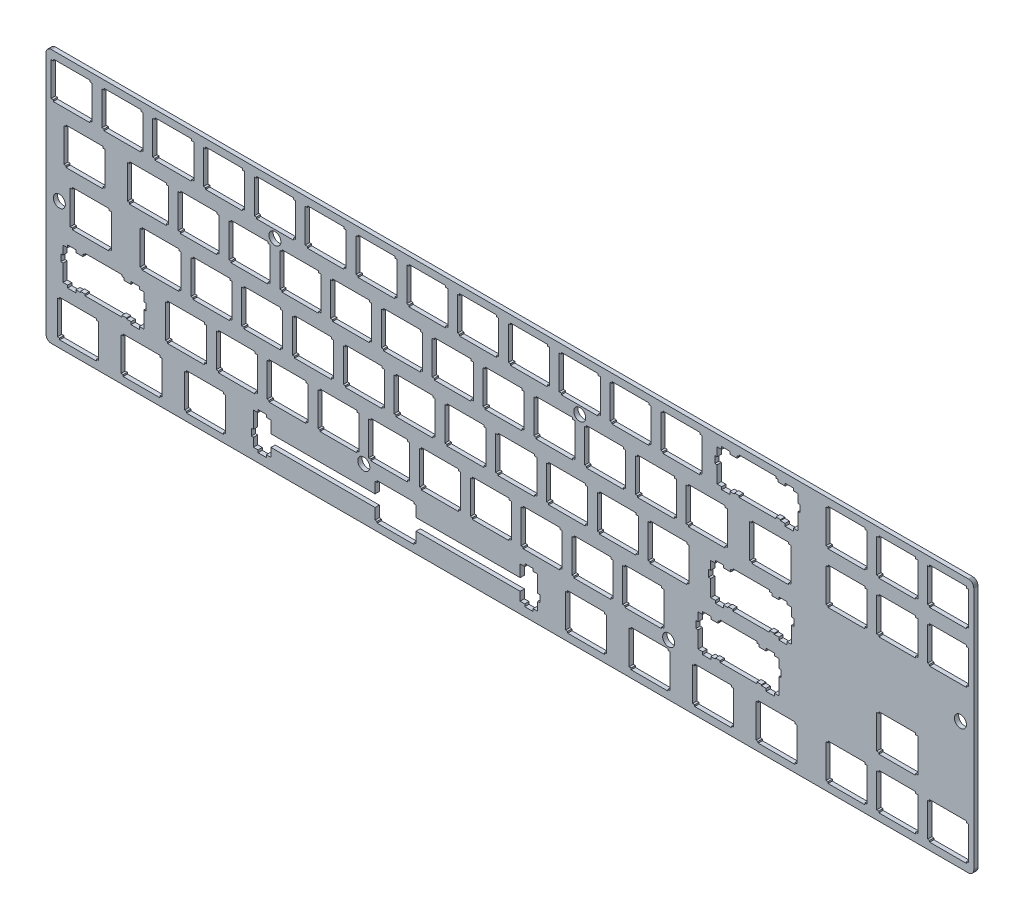
SolidWorks part; units mm, degrees
material "Brass"
ref_plane "Front Plane" through (0, 0, 0) normal (0, 0, 1) x (1, 0, 0)
ref_plane "Top Plane" through (0, 0, 0) normal (0, 1, 0) x (1, 0, 0)
ref_plane "Right Plane" through (0, 0, 0) normal (1, 0, 0) x (0, 0, -1)
sketch "Model" plane through (0, 0, 0) normal (0, 0, 1) x (1, 0, 0)
  line L0 (162.6206, 107.1381) -> (162.6206, 107.7376)
  line L1 (162.6206, 107.7376) -> (163.4196, 107.7376)
  line L2 (163.4196, 107.7376) -> (163.4196, 111.8386)
  line L3 (163.4196, 111.8386) -> (202.4455, 111.8386)
  line L4 (202.4455, 111.8386) -> (202.4455, 108.6085)
  line L5 (202.4455, 108.6085) -> (204.1696, 108.6085)
  line L6 (204.1696, 108.6085) -> (204.1696, 107.6893)
  line L7 (204.1696, 107.6893) -> (207.2701, 107.6893)
  line L8 (207.2701, 107.6893) -> (207.2701, 108.6085)
  line L9 (207.2701, 108.6085) -> (208.9956, 108.6085)
  line L10 (208.9956, 108.6085) -> (208.9956, 111.8386)
  line L11 (208.9956, 111.8386) -> (209.8196, 111.8386)
  line L12 (209.8196, 111.8386) -> (209.8196, 114.4389)
  line L13 (209.8196, 114.4389) -> (208.9956, 114.4389)
  line L14 (208.9956, 114.4389) -> (208.9956, 120.7076)
  line L15 (208.9956, 120.7076) -> (207.2701, 120.7076)
  line L16 (207.2701, 120.7076) -> (207.2701, 121.6888)
  line L17 (207.2701, 121.6888) -> (204.1696, 121.6888)
  line L18 (204.1696, 121.6888) -> (204.1696, 120.7076)
  line L19 (204.1696, 120.7076) -> (202.4455, 120.7076)
  line L20 (202.4455, 120.7076) -> (202.4455, 116.2387)
  line L21 (202.4455, 116.2387) -> (163.4196, 116.2387)
  line L22 (163.4196, 116.2387) -> (163.4196, 120.3383)
  line L23 (163.4196, 120.3383) -> (162.6206, 120.3383)
  line L24 (162.6206, 120.3383) -> (162.6206, 120.9391)
  line L25 (162.6206, 120.9391) -> (148.8206, 120.9391)
  line L26 (148.8206, 120.9391) -> (148.8206, 120.3383)
  line L27 (148.8206, 120.3383) -> (148.0196, 120.3383)
  line L28 (148.0196, 120.3383) -> (148.0196, 116.2387)
  line L29 (148.0196, 116.2387) -> (108.9956, 116.2387)
  line L30 (108.9956, 116.2387) -> (108.9956, 120.7076)
  line L31 (108.9956, 120.7076) -> (107.2696, 120.7076)
  line L32 (107.2696, 120.7076) -> (107.2696, 121.6888)
  line L33 (107.2696, 121.6888) -> (104.1696, 121.6888)
  line L34 (104.1696, 121.6888) -> (104.1696, 120.7076)
  line L35 (104.1696, 120.7076) -> (102.4456, 120.7076)
  line L36 (102.4456, 120.7076) -> (102.4456, 114.4389)
  line L37 (102.4456, 114.4389) -> (101.6206, 114.4389)
  line L38 (101.6206, 114.4389) -> (101.6206, 111.8386)
  line L39 (101.6206, 111.8386) -> (102.4456, 111.8386)
  line L40 (102.4456, 111.8386) -> (102.4456, 108.6085)
  line L41 (102.4456, 108.6085) -> (104.1696, 108.6085)
  line L42 (104.1696, 108.6085) -> (104.1696, 107.6893)
  line L43 (104.1696, 107.6893) -> (107.2696, 107.6893)
  line L44 (107.2696, 107.6893) -> (107.2696, 108.6085)
  line L45 (107.2696, 108.6085) -> (108.9956, 108.6085)
  line L46 (108.9956, 108.6085) -> (108.9956, 111.8386)
  line L47 (108.9956, 111.8386) -> (148.0196, 111.8386)
  line L48 (148.0196, 111.8386) -> (148.0196, 107.7376)
  line L49 (148.0196, 107.7376) -> (148.8206, 107.7376)
  line L50 (148.8206, 107.7376) -> (148.8206, 107.1381)
  line L51 (148.8206, 107.1381) -> (162.6206, 107.1381)
  line L52 (355.9896, 120.9391) -> (355.9896, 120.3396)
  line L53 (355.9896, 120.3396) -> (355.1906, 120.3396)
  line L54 (355.1906, 120.3396) -> (355.1906, 107.7389)
  line L55 (355.1906, 107.7389) -> (355.9896, 107.7389)
  line L56 (355.9896, 107.7389) -> (355.9896, 107.1381)
  line L57 (355.9896, 107.1381) -> (369.7906, 107.1381)
  line L58 (369.7906, 107.1381) -> (369.7906, 107.7389)
  line L59 (369.7906, 107.7389) -> (370.5896, 107.7389)
  line L60 (370.5896, 107.7389) -> (370.5896, 120.3396)
  line L61 (370.5896, 120.3396) -> (369.7906, 120.3396)
  line L62 (369.7906, 120.3396) -> (369.7906, 120.9391)
  line L63 (369.7906, 120.9391) -> (355.9896, 120.9391)
  line L64 (336.9396, 120.9391) -> (336.9396, 120.3396)
  line L65 (336.9396, 120.3396) -> (336.1406, 120.3396)
  line L66 (336.1406, 120.3396) -> (336.1406, 107.7389)
  line L67 (336.1406, 107.7389) -> (336.9396, 107.7389)
  line L68 (336.9396, 107.7389) -> (336.9396, 107.1381)
  line L69 (336.9396, 107.1381) -> (350.7406, 107.1381)
  line L70 (350.7406, 107.1381) -> (350.7406, 107.7389)
  line L71 (350.7406, 107.7389) -> (351.5396, 107.7389)
  line L72 (351.5396, 107.7389) -> (351.5396, 120.3396)
  line L73 (351.5396, 120.3396) -> (350.7406, 120.3396)
  line L74 (350.7406, 120.3396) -> (350.7406, 120.9391)
  line L75 (350.7406, 120.9391) -> (336.9396, 120.9391)
  line L76 (317.8896, 120.9391) -> (317.8896, 120.3396)
  line L77 (317.8896, 120.3396) -> (317.0906, 120.3396)
  line L78 (317.0906, 120.3396) -> (317.0906, 107.7389)
  line L79 (317.0906, 107.7389) -> (317.8896, 107.7389)
  line L80 (317.8896, 107.7389) -> (317.8896, 107.1381)
  line L81 (317.8896, 107.1381) -> (331.6906, 107.1381)
  line L82 (331.6906, 107.1381) -> (331.6906, 107.7389)
  line L83 (331.6906, 107.7389) -> (332.4896, 107.7389)
  line L84 (332.4896, 107.7389) -> (332.4896, 120.3396)
  line L85 (332.4896, 120.3396) -> (331.6906, 120.3396)
  line L86 (331.6906, 120.3396) -> (331.6906, 120.9391)
  line L87 (331.6906, 120.9391) -> (317.8896, 120.9391)
  line L88 (291.6956, 120.9391) -> (291.6956, 120.3396)
  line L89 (291.6956, 120.3396) -> (290.8966, 120.3396)
  line L90 (290.8966, 120.3396) -> (290.8966, 107.7389)
  line L91 (290.8966, 107.7389) -> (291.6956, 107.7389)
  line L92 (291.6956, 107.7389) -> (291.6956, 107.1381)
  line L93 (291.6956, 107.1381) -> (305.4956, 107.1381)
  line L94 (305.4956, 107.1381) -> (305.4956, 107.7389)
  line L95 (305.4956, 107.7389) -> (306.2966, 107.7389)
  line L96 (306.2966, 107.7389) -> (306.2966, 120.3396)
  line L97 (306.2966, 120.3396) -> (305.4956, 120.3396)
  line L98 (305.4956, 120.3396) -> (305.4956, 120.9391)
  line L99 (305.4956, 120.9391) -> (291.6956, 120.9391)
  line L100 (267.8846, 120.9391) -> (267.8846, 120.3396)
  line L101 (267.8846, 120.3396) -> (267.0846, 120.3396)
  line L102 (267.0846, 120.3396) -> (267.0846, 107.7389)
  line L103 (267.0846, 107.7389) -> (267.8846, 107.7389)
  line L104 (267.8846, 107.7389) -> (267.8846, 107.1381)
  line L105 (267.8846, 107.1381) -> (281.6846, 107.1381)
  line L106 (281.6846, 107.1381) -> (281.6846, 107.7389)
  line L107 (281.6846, 107.7389) -> (282.4836, 107.7389)
  line L108 (282.4836, 107.7389) -> (282.4836, 120.3396)
  line L109 (282.4836, 120.3396) -> (281.6846, 120.3396)
  line L110 (281.6846, 120.3396) -> (281.6846, 120.9391)
  line L111 (281.6846, 120.9391) -> (267.8846, 120.9391)
  line L112 (244.0706, 120.9391) -> (244.0706, 120.3396)
  line L113 (244.0706, 120.3396) -> (243.2716, 120.3396)
  line L114 (243.2716, 120.3396) -> (243.2716, 107.7389)
  line L115 (243.2716, 107.7389) -> (244.0706, 107.7389)
  line L116 (244.0706, 107.7389) -> (244.0706, 107.1381)
  line L117 (244.0706, 107.1381) -> (257.8706, 107.1381)
  line L118 (257.8706, 107.1381) -> (257.8706, 107.7389)
  line L119 (257.8706, 107.7389) -> (258.6716, 107.7389)
  line L120 (258.6716, 107.7389) -> (258.6716, 120.3396)
  line L121 (258.6716, 120.3396) -> (257.8706, 120.3396)
  line L122 (257.8706, 120.3396) -> (257.8706, 120.9391)
  line L123 (257.8706, 120.9391) -> (244.0706, 120.9391)
  line L124 (220.2596, 120.9391) -> (220.2596, 120.3396)
  line L125 (220.2596, 120.3396) -> (219.4596, 120.3396)
  line L126 (219.4596, 120.3396) -> (219.4596, 107.7389)
  line L127 (219.4596, 107.7389) -> (220.2596, 107.7389)
  line L128 (220.2596, 107.7389) -> (220.2596, 107.1381)
  line L129 (220.2596, 107.1381) -> (234.0596, 107.1381)
  line L130 (234.0596, 107.1381) -> (234.0596, 107.7389)
  line L131 (234.0596, 107.7389) -> (234.8586, 107.7389)
  line L132 (234.8586, 107.7389) -> (234.8586, 120.3396)
  line L133 (234.8586, 120.3396) -> (234.0596, 120.3396)
  line L134 (234.0596, 120.3396) -> (234.0596, 120.9391)
  line L135 (234.0596, 120.9391) -> (220.2596, 120.9391)
  line L136 (77.3847, 120.9391) -> (77.3847, 120.3396)
  line L137 (77.3847, 120.3396) -> (76.5842, 120.3396)
  line L138 (76.5842, 120.3396) -> (76.5842, 107.7389)
  line L139 (76.5842, 107.7389) -> (77.3847, 107.7389)
  line L140 (77.3847, 107.7389) -> (77.3847, 107.1381)
  line L141 (77.3847, 107.1381) -> (91.1843, 107.1381)
  line L142 (91.1843, 107.1381) -> (91.1843, 107.7389)
  line L143 (91.1843, 107.7389) -> (91.9837, 107.7389)
  line L144 (91.9837, 107.7389) -> (91.9837, 120.3396)
  line L145 (91.9837, 120.3396) -> (91.1843, 120.3396)
  line L146 (91.1843, 120.3396) -> (91.1843, 120.9391)
  line L147 (91.1843, 120.9391) -> (77.3847, 120.9391)
  line L148 (53.5708, 120.9391) -> (53.5708, 120.3396)
  line L149 (53.5708, 120.3396) -> (52.7716, 120.3396)
  line L150 (52.7716, 120.3396) -> (52.7716, 107.7389)
  line L151 (52.7716, 107.7389) -> (53.5708, 107.7389)
  line L152 (53.5708, 107.7389) -> (53.5708, 107.1381)
  line L153 (53.5708, 107.1381) -> (67.3704, 107.1381)
  line L154 (67.3704, 107.1381) -> (67.3704, 107.7389)
  line L155 (67.3704, 107.7389) -> (68.1712, 107.7389)
  line L156 (68.1712, 107.7389) -> (68.1712, 120.3396)
  line L157 (68.1712, 120.3396) -> (67.3704, 120.3396)
  line L158 (67.3704, 120.3396) -> (67.3704, 120.9391)
  line L159 (67.3704, 120.9391) -> (53.5708, 120.9391)
  line L160 (29.7597, 120.9391) -> (29.7597, 120.3396)
  line L161 (29.7597, 120.3396) -> (28.959, 120.3396)
  line L162 (28.959, 120.3396) -> (28.959, 107.7389)
  line L163 (28.959, 107.7389) -> (29.7597, 107.7389)
  line L164 (29.7597, 107.7389) -> (29.7597, 107.1381)
  line L165 (29.7597, 107.1381) -> (43.5594, 107.1381)
  line L166 (43.5594, 107.1381) -> (43.5594, 107.7389)
  line L167 (43.5594, 107.7389) -> (44.3586, 107.7389)
  line L168 (44.3586, 107.7389) -> (44.3586, 120.3396)
  line L169 (44.3586, 120.3396) -> (43.5594, 120.3396)
  line L170 (43.5594, 120.3396) -> (43.5594, 120.9391)
  line L171 (43.5594, 120.9391) -> (29.7597, 120.9391)
  line L172 (277.4086, 139.9906) -> (277.4086, 139.3898)
  line L173 (277.4086, 139.3898) -> (276.6096, 139.3898)
  line L174 (276.6096, 139.3898) -> (276.6096, 138.5187)
  line L175 (275.6846, 138.5187) -> (273.9596, 138.5187)
  line L176 (273.9596, 138.5187) -> (273.9596, 139.4378)
  line L177 (273.9596, 139.4378) -> (270.8586, 139.4378)
  line L178 (270.8586, 139.4378) -> (270.8586, 138.5187)
  line L179 (270.8586, 138.5187) -> (269.1346, 138.5187)
  line L180 (269.1346, 138.5187) -> (269.1346, 135.2886)
  line L181 (269.1346, 135.2886) -> (268.3086, 135.2886)
  line L182 (268.3086, 135.2886) -> (268.3086, 132.6882)
  line L183 (268.3086, 132.6882) -> (269.1346, 132.6882)
  line L184 (269.1346, 132.6882) -> (269.1346, 126.4182)
  line L185 (269.1346, 126.4182) -> (270.8586, 126.4182)
  line L186 (270.8586, 126.4182) -> (270.8586, 125.4384)
  line L187 (270.8586, 125.4384) -> (273.9596, 125.4384)
  line L188 (273.9596, 125.4384) -> (273.9596, 126.4182)
  line L189 (273.9596, 126.4182) -> (275.6846, 126.4182)
  line L190 (275.6846, 126.4182) -> (275.6846, 126.7888)
  line L191 (276.6096, 126.7888) -> (277.4086, 126.7888)
  line L192 (277.4086, 126.7888) -> (277.4086, 126.188)
  line L193 (277.4086, 126.188) -> (291.2096, 126.188)
  line L194 (291.2096, 126.188) -> (291.2096, 126.7888)
  line L195 (291.2096, 126.7888) -> (292.0086, 126.7888)
  line L196 (292.9346, 126.7888) -> (292.9346, 126.4182)
  line L197 (292.9346, 126.4182) -> (294.6586, 126.4182)
  line L198 (294.6586, 126.4182) -> (294.6586, 125.4384)
  line L199 (294.6586, 125.4384) -> (297.7596, 125.4384)
  line L200 (297.7596, 125.4384) -> (297.7596, 126.4182)
  line L201 (297.7596, 126.4182) -> (299.4846, 126.4182)
  line L202 (299.4846, 126.4182) -> (299.4846, 132.6882)
  line L203 (299.4846, 132.6882) -> (300.3086, 132.6882)
  line L204 (300.3086, 132.6882) -> (300.3086, 135.2886)
  line L205 (300.3086, 135.2886) -> (299.4846, 135.2886)
  line L206 (299.4846, 135.2886) -> (299.4846, 138.5187)
  line L207 (299.4846, 138.5187) -> (297.7596, 138.5187)
  line L208 (297.7596, 138.5187) -> (297.7596, 139.4378)
  line L209 (297.7596, 139.4378) -> (294.6586, 139.4378)
  line L210 (294.6586, 139.4378) -> (294.6586, 138.5187)
  line L211 (294.6586, 138.5187) -> (292.9346, 138.5187)
  line L212 (292.0086, 138.5187) -> (292.0086, 139.3898)
  line L213 (292.0086, 139.3898) -> (291.2096, 139.3898)
  line L214 (291.2096, 139.3898) -> (291.2096, 139.9906)
  line L215 (291.2096, 139.9906) -> (277.4086, 139.9906)
  line L216 (39.2847, 139.9906) -> (39.2847, 139.3898)
  line L217 (39.2847, 139.3898) -> (38.4841, 139.3898)
  line L218 (38.4841, 139.3898) -> (38.4841, 138.5187)
  line L219 (299.1536, 195.6688) -> (300.0786, 195.6688)
  line L220 (296.7716, 157.5688) -> (297.6956, 157.5688)
  line L221 (37.5594, 138.5187) -> (35.8341, 138.5187)
  line L222 (35.8341, 138.5187) -> (35.8341, 139.4378)
  line L223 (35.8341, 139.4378) -> (32.7335, 139.4378)
  line L224 (32.7335, 139.4378) -> (32.7335, 138.5187)
  line L225 (32.7335, 138.5187) -> (31.0095, 138.5187)
  line L226 (31.0095, 138.5187) -> (31.0095, 135.2886)
  line L227 (31.0095, 135.2886) -> (30.1841, 135.2886)
  line L228 (30.1841, 135.2886) -> (30.1841, 132.6882)
  line L229 (30.1841, 132.6882) -> (31.0095, 132.6882)
  line L230 (31.0095, 132.6882) -> (31.0095, 126.4182)
  line L231 (31.0095, 126.4182) -> (32.7335, 126.4182)
  line L232 (32.7335, 126.4182) -> (32.7335, 125.4384)
  line L233 (32.7335, 125.4384) -> (35.8341, 125.4384)
  line L234 (35.8341, 125.4384) -> (35.8341, 126.4182)
  line L235 (35.8341, 126.4182) -> (37.5594, 126.4182)
  line L236 (37.5594, 126.4182) -> (37.5594, 126.7888)
  line L237 (292.0086, 138.5187) -> (292.9346, 138.5187)
  line L238 (38.4841, 126.7888) -> (39.2847, 126.7888)
  line L239 (39.2847, 126.7888) -> (39.2847, 126.188)
  line L240 (39.2847, 126.188) -> (53.0844, 126.188)
  line L241 (53.0844, 126.188) -> (53.0844, 126.7888)
  line L242 (53.0844, 126.7888) -> (53.8836, 126.7888)
  line L243 (54.8097, 126.7888) -> (54.8097, 126.4182)
  line L244 (54.8097, 126.4182) -> (56.5336, 126.4182)
  line L245 (56.5336, 126.4182) -> (56.5336, 125.4384)
  line L246 (56.5336, 125.4384) -> (59.6342, 125.4384)
  line L247 (59.6342, 125.4384) -> (59.6342, 126.4182)
  line L248 (59.6342, 126.4182) -> (61.3594, 126.4182)
  line L249 (61.3594, 126.4182) -> (61.3594, 132.6882)
  line L250 (61.3594, 132.6882) -> (62.1835, 132.6882)
  line L251 (62.1835, 132.6882) -> (62.1835, 135.2886)
  line L252 (62.1835, 135.2886) -> (61.3594, 135.2886)
  line L253 (61.3594, 135.2886) -> (61.3594, 138.5187)
  line L254 (61.3594, 138.5187) -> (59.6342, 138.5187)
  line L255 (59.6342, 138.5187) -> (59.6342, 139.4378)
  line L256 (59.6342, 139.4378) -> (56.5336, 139.4378)
  line L257 (56.5336, 139.4378) -> (56.5336, 138.5187)
  line L258 (56.5336, 138.5187) -> (54.8097, 138.5187)
  line L259 (53.8836, 138.5187) -> (53.8836, 139.3898)
  line L260 (53.8836, 139.3898) -> (53.0844, 139.3898)
  line L261 (53.0844, 139.3898) -> (53.0844, 139.9906)
  line L262 (53.0844, 139.9906) -> (39.2847, 139.9906)
  line L263 (336.9396, 139.9906) -> (336.9396, 139.3898)
  line L264 (336.9396, 139.3898) -> (336.1406, 139.3898)
  line L265 (336.1406, 139.3898) -> (336.1406, 126.7888)
  line L266 (336.1406, 126.7888) -> (336.9396, 126.7888)
  line L267 (336.9396, 126.7888) -> (336.9396, 126.188)
  line L268 (336.9396, 126.188) -> (350.7406, 126.188)
  line L269 (350.7406, 126.188) -> (350.7406, 126.7888)
  line L270 (350.7406, 126.7888) -> (351.5396, 126.7888)
  line L271 (351.5396, 126.7888) -> (351.5396, 139.3898)
  line L272 (351.5396, 139.3898) -> (350.7406, 139.3898)
  line L273 (350.7406, 139.3898) -> (350.7406, 139.9906)
  line L274 (350.7406, 139.9906) -> (336.9396, 139.9906)
  line L275 (241.6896, 139.9906) -> (241.6896, 139.3898)
  line L276 (241.6896, 139.3898) -> (240.8906, 139.3898)
  line L277 (240.8906, 139.3898) -> (240.8906, 126.7888)
  line L278 (240.8906, 126.7888) -> (241.6896, 126.7888)
  line L279 (241.6896, 126.7888) -> (241.6896, 126.188)
  line L280 (241.6896, 126.188) -> (255.4906, 126.188)
  line L281 (255.4906, 126.188) -> (255.4906, 126.7888)
  line L282 (255.4906, 126.7888) -> (256.2896, 126.7888)
  line L283 (256.2896, 126.7888) -> (256.2896, 139.3898)
  line L284 (256.2896, 139.3898) -> (255.4906, 139.3898)
  line L285 (255.4906, 139.3898) -> (255.4906, 139.9906)
  line L286 (255.4906, 139.9906) -> (241.6896, 139.9906)
  line L287 (222.6396, 139.9906) -> (222.6396, 139.3898)
  line L288 (222.6396, 139.3898) -> (221.8406, 139.3898)
  line L289 (221.8406, 139.3898) -> (221.8406, 126.7888)
  line L290 (221.8406, 126.7888) -> (222.6396, 126.7888)
  line L291 (222.6396, 126.7888) -> (222.6396, 126.188)
  line L292 (222.6396, 126.188) -> (236.4406, 126.188)
  line L293 (236.4406, 126.188) -> (236.4406, 126.7888)
  line L294 (236.4406, 126.7888) -> (237.2396, 126.7888)
  line L295 (237.2396, 126.7888) -> (237.2396, 139.3898)
  line L296 (237.2396, 139.3898) -> (236.4406, 139.3898)
  line L297 (236.4406, 139.3898) -> (236.4406, 139.9906)
  line L298 (236.4406, 139.9906) -> (222.6396, 139.9906)
  line L299 (203.5896, 139.9906) -> (203.5896, 139.3898)
  line L300 (203.5896, 139.3898) -> (202.7906, 139.3898)
  line L301 (202.7906, 139.3898) -> (202.7906, 126.7888)
  line L302 (202.7906, 126.7888) -> (203.5896, 126.7888)
  line L303 (203.5896, 126.7888) -> (203.5896, 126.188)
  line L304 (203.5896, 126.188) -> (217.3906, 126.188)
  line L305 (217.3906, 126.188) -> (217.3906, 126.7888)
  line L306 (217.3906, 126.7888) -> (218.1896, 126.7888)
  line L307 (218.1896, 126.7888) -> (218.1896, 139.3898)
  line L308 (218.1896, 139.3898) -> (217.3906, 139.3898)
  line L309 (217.3906, 139.3898) -> (217.3906, 139.9906)
  line L310 (217.3906, 139.9906) -> (203.5896, 139.9906)
  line L311 (184.5396, 139.9906) -> (184.5396, 139.3898)
  line L312 (184.5396, 139.3898) -> (183.7406, 139.3898)
  line L313 (183.7406, 139.3898) -> (183.7406, 126.7888)
  line L314 (183.7406, 126.7888) -> (184.5396, 126.7888)
  line L315 (184.5396, 126.7888) -> (184.5396, 126.188)
  line L316 (184.5396, 126.188) -> (198.3406, 126.188)
  line L317 (198.3406, 126.188) -> (198.3406, 126.7888)
  line L318 (198.3406, 126.7888) -> (199.1396, 126.7888)
  line L319 (199.1396, 126.7888) -> (199.1396, 139.3898)
  line L320 (199.1396, 139.3898) -> (198.3406, 139.3898)
  line L321 (198.3406, 139.3898) -> (198.3406, 139.9906)
  line L322 (198.3406, 139.9906) -> (184.5396, 139.9906)
  line L323 (165.4896, 139.9906) -> (165.4896, 139.3898)
  line L324 (165.4896, 139.3898) -> (164.6906, 139.3898)
  line L325 (164.6906, 139.3898) -> (164.6906, 126.7888)
  line L326 (164.6906, 126.7888) -> (165.4896, 126.7888)
  line L327 (165.4896, 126.7888) -> (165.4896, 126.188)
  line L328 (165.4896, 126.188) -> (179.2906, 126.188)
  line L329 (179.2906, 126.188) -> (179.2906, 126.7888)
  line L330 (179.2906, 126.7888) -> (180.0896, 126.7888)
  line L331 (180.0896, 126.7888) -> (180.0896, 139.3898)
  line L332 (180.0896, 139.3898) -> (179.2906, 139.3898)
  line L333 (179.2906, 139.3898) -> (179.2906, 139.9906)
  line L334 (179.2906, 139.9906) -> (165.4896, 139.9906)
  line L335 (146.4396, 139.9906) -> (146.4396, 139.3898)
  line L336 (146.4396, 139.3898) -> (145.6406, 139.3898)
  line L337 (145.6406, 139.3898) -> (145.6406, 126.7888)
  line L338 (145.6406, 126.7888) -> (146.4396, 126.7888)
  line L339 (146.4396, 126.7888) -> (146.4396, 126.188)
  line L340 (146.4396, 126.188) -> (160.2406, 126.188)
  line L341 (160.2406, 126.188) -> (160.2406, 126.7888)
  line L342 (160.2406, 126.7888) -> (161.0396, 126.7888)
  line L343 (161.0396, 126.7888) -> (161.0396, 139.3898)
  line L344 (161.0396, 139.3898) -> (160.2406, 139.3898)
  line L345 (160.2406, 139.3898) -> (160.2406, 139.9906)
  line L346 (160.2406, 139.9906) -> (146.4396, 139.9906)
  line L347 (127.3896, 139.9906) -> (127.3896, 139.3898)
  line L348 (127.3896, 139.3898) -> (126.5906, 139.3898)
  line L349 (126.5906, 139.3898) -> (126.5906, 126.7888)
  line L350 (126.5906, 126.7888) -> (127.3896, 126.7888)
  line L351 (127.3896, 126.7888) -> (127.3896, 126.188)
  line L352 (127.3896, 126.188) -> (141.1906, 126.188)
  line L353 (141.1906, 126.188) -> (141.1906, 126.7888)
  line L354 (141.1906, 126.7888) -> (141.9896, 126.7888)
  line L355 (141.9896, 126.7888) -> (141.9896, 139.3898)
  line L356 (141.9896, 139.3898) -> (141.1906, 139.3898)
  line L357 (141.1906, 139.3898) -> (141.1906, 139.9906)
  line L358 (141.1906, 139.9906) -> (127.3896, 139.9906)
  line L359 (108.3395, 139.9906) -> (108.3395, 139.3898)
  line L360 (108.3395, 139.3898) -> (107.5405, 139.3898)
  line L361 (107.5405, 139.3898) -> (107.5405, 126.7888)
  line L362 (107.5405, 126.7888) -> (108.3395, 126.7888)
  line L363 (108.3395, 126.7888) -> (108.3395, 126.188)
  line L364 (108.3395, 126.188) -> (122.1405, 126.188)
  line L365 (122.1405, 126.188) -> (122.1405, 126.7888)
  line L366 (122.1405, 126.7888) -> (122.9399, 126.7888)
  line L367 (122.9399, 126.7888) -> (122.9399, 139.3898)
  line L368 (122.9399, 139.3898) -> (122.1405, 139.3898)
  line L369 (122.1405, 139.3898) -> (122.1405, 139.9906)
  line L370 (122.1405, 139.9906) -> (108.3395, 139.9906)
  line L371 (89.2895, 139.9906) -> (89.2895, 139.3898)
  line L372 (89.2895, 139.3898) -> (88.4905, 139.3898)
  line L373 (88.4905, 139.3898) -> (88.4905, 126.7888)
  line L374 (88.4905, 126.7888) -> (89.2895, 126.7888)
  line L375 (89.2895, 126.7888) -> (89.2895, 126.188)
  line L376 (89.2895, 126.188) -> (103.0905, 126.188)
  line L377 (103.0905, 126.188) -> (103.0905, 126.7888)
  line L378 (103.0905, 126.7888) -> (103.8899, 126.7888)
  line L379 (103.8899, 126.7888) -> (103.8899, 139.3898)
  line L380 (103.8899, 139.3898) -> (103.0905, 139.3898)
  line L381 (103.0905, 139.3898) -> (103.0905, 139.9906)
  line L382 (103.0905, 139.9906) -> (89.2895, 139.9906)
  line L383 (70.2395, 139.9906) -> (70.2395, 139.3898)
  line L384 (70.2395, 139.3898) -> (69.4405, 139.3898)
  line L385 (69.4405, 139.3898) -> (69.4405, 126.7888)
  line L386 (69.4405, 126.7888) -> (70.2395, 126.7888)
  line L387 (70.2395, 126.7888) -> (70.2395, 126.188)
  line L388 (70.2395, 126.188) -> (84.0405, 126.188)
  line L389 (84.0405, 126.188) -> (84.0405, 126.7888)
  line L390 (84.0405, 126.7888) -> (84.8399, 126.7888)
  line L391 (84.8399, 126.7888) -> (84.8399, 139.3898)
  line L392 (84.8399, 139.3898) -> (84.0405, 139.3898)
  line L393 (84.0405, 139.3898) -> (84.0405, 139.9906)
  line L394 (84.0405, 139.9906) -> (70.2395, 139.9906)
  line L395 (282.1706, 159.0392) -> (282.1706, 158.4384)
  line L396 (282.1706, 158.4384) -> (281.3716, 158.4384)
  line L397 (281.3716, 158.4384) -> (281.3716, 157.5688)
  line L398 (280.4456, 157.5688) -> (278.7206, 157.5688)
  line L399 (278.7206, 157.5688) -> (278.7206, 158.4892)
  line L400 (278.7206, 158.4892) -> (275.6206, 158.4892)
  line L401 (275.6206, 158.4892) -> (275.6206, 157.5688)
  line L402 (275.6206, 157.5688) -> (273.8956, 157.5688)
  line L403 (273.8956, 157.5688) -> (273.8956, 154.3387)
  line L404 (273.8956, 154.3387) -> (273.0716, 154.3387)
  line L405 (273.0716, 154.3387) -> (273.0716, 151.7395)
  line L406 (273.0716, 151.7395) -> (273.8956, 151.7395)
  line L407 (273.8956, 151.7395) -> (273.8956, 145.4696)
  line L408 (273.8956, 145.4696) -> (275.6206, 145.4696)
  line L409 (275.6206, 145.4696) -> (275.6206, 144.4885)
  line L410 (275.6206, 144.4885) -> (278.7206, 144.4885)
  line L411 (278.7206, 144.4885) -> (278.7206, 145.4696)
  line L412 (278.7206, 145.4696) -> (280.4456, 145.4696)
  line L413 (280.4456, 145.4696) -> (280.4456, 145.8389)
  line L414 (281.3716, 145.8389) -> (282.1706, 145.8389)
  line L415 (282.1706, 145.8389) -> (282.1706, 145.2395)
  line L416 (282.1706, 145.2395) -> (295.9706, 145.2395)
  line L417 (295.9706, 145.2395) -> (295.9706, 145.8389)
  line L418 (295.9706, 145.8389) -> (296.7716, 145.8389)
  line L419 (297.6956, 145.8389) -> (297.6956, 145.4696)
  line L420 (297.6956, 145.4696) -> (299.4216, 145.4696)
  line L421 (299.4216, 145.4696) -> (299.4216, 144.4885)
  line L422 (299.4216, 144.4885) -> (302.5216, 144.4885)
  line L423 (302.5216, 144.4885) -> (302.5216, 145.4696)
  line L424 (302.5216, 145.4696) -> (304.2456, 145.4696)
  line L425 (304.2456, 145.4696) -> (304.2456, 151.7395)
  line L426 (304.2456, 151.7395) -> (305.0706, 151.7395)
  line L427 (305.0706, 151.7395) -> (305.0706, 154.3387)
  line L428 (305.0706, 154.3387) -> (304.2456, 154.3387)
  line L429 (304.2456, 154.3387) -> (304.2456, 157.5688)
  line L430 (304.2456, 157.5688) -> (302.5216, 157.5688)
  line L431 (302.5216, 157.5688) -> (302.5216, 158.4892)
  line L432 (302.5216, 158.4892) -> (299.4216, 158.4892)
  line L433 (299.4216, 158.4892) -> (299.4216, 157.5688)
  line L434 (299.4216, 157.5688) -> (297.6956, 157.5688)
  line L435 (296.7716, 157.5688) -> (296.7716, 158.4384)
  line L436 (296.7716, 158.4384) -> (295.9706, 158.4384)
  line L437 (295.9706, 158.4384) -> (295.9706, 159.0392)
  line L438 (295.9706, 159.0392) -> (282.1706, 159.0392)
  line L439 (251.2146, 159.0392) -> (251.2146, 158.4384)
  line L440 (251.2146, 158.4384) -> (250.4156, 158.4384)
  line L441 (250.4156, 158.4384) -> (250.4156, 145.8389)
  line L442 (250.4156, 145.8389) -> (251.2146, 145.8389)
  line L443 (251.2146, 145.8389) -> (251.2146, 145.2395)
  line L444 (251.2146, 145.2395) -> (265.0156, 145.2395)
  line L445 (265.0156, 145.2395) -> (265.0156, 145.8389)
  line L446 (265.0156, 145.8389) -> (265.8146, 145.8389)
  line L447 (265.8146, 145.8389) -> (265.8146, 158.4384)
  line L448 (265.8146, 158.4384) -> (265.0156, 158.4384)
  line L449 (265.0156, 158.4384) -> (265.0156, 159.0392)
  line L450 (265.0156, 159.0392) -> (251.2146, 159.0392)
  line L451 (232.1646, 159.0392) -> (232.1646, 158.4384)
  line L452 (232.1646, 158.4384) -> (231.3656, 158.4384)
  line L453 (231.3656, 158.4384) -> (231.3656, 145.8389)
  line L454 (231.3656, 145.8389) -> (232.1646, 145.8389)
  line L455 (232.1646, 145.8389) -> (232.1646, 145.2395)
  line L456 (232.1646, 145.2395) -> (245.9656, 145.2395)
  line L457 (245.9656, 145.2395) -> (245.9656, 145.8389)
  line L458 (245.9656, 145.8389) -> (246.7646, 145.8389)
  line L459 (246.7646, 145.8389) -> (246.7646, 158.4384)
  line L460 (246.7646, 158.4384) -> (245.9656, 158.4384)
  line L461 (245.9656, 158.4384) -> (245.9656, 159.0392)
  line L462 (245.9656, 159.0392) -> (232.1646, 159.0392)
  line L463 (213.1146, 159.0392) -> (213.1146, 158.4384)
  line L464 (213.1146, 158.4384) -> (212.3156, 158.4384)
  line L465 (212.3156, 158.4384) -> (212.3156, 145.8389)
  line L466 (212.3156, 145.8389) -> (213.1146, 145.8389)
  line L467 (213.1146, 145.8389) -> (213.1146, 145.2395)
  line L468 (213.1146, 145.2395) -> (226.9156, 145.2395)
  line L469 (226.9156, 145.2395) -> (226.9156, 145.8389)
  line L470 (226.9156, 145.8389) -> (227.7146, 145.8389)
  line L471 (227.7146, 145.8389) -> (227.7146, 158.4384)
  line L472 (227.7146, 158.4384) -> (226.9156, 158.4384)
  line L473 (226.9156, 158.4384) -> (226.9156, 159.0392)
  line L474 (226.9156, 159.0392) -> (213.1146, 159.0392)
  line L475 (194.0646, 159.0392) -> (194.0646, 158.4384)
  line L476 (194.0646, 158.4384) -> (193.2656, 158.4384)
  line L477 (193.2656, 158.4384) -> (193.2656, 145.8389)
  line L478 (193.2656, 145.8389) -> (194.0646, 145.8389)
  line L479 (194.0646, 145.8389) -> (194.0646, 145.2395)
  line L480 (194.0646, 145.2395) -> (207.8656, 145.2395)
  line L481 (207.8656, 145.2395) -> (207.8656, 145.8389)
  line L482 (207.8656, 145.8389) -> (208.6646, 145.8389)
  line L483 (208.6646, 145.8389) -> (208.6646, 158.4384)
  line L484 (208.6646, 158.4384) -> (207.8656, 158.4384)
  line L485 (207.8656, 158.4384) -> (207.8656, 159.0392)
  line L486 (207.8656, 159.0392) -> (194.0646, 159.0392)
  line L487 (175.0146, 159.0392) -> (175.0146, 158.4384)
  line L488 (175.0146, 158.4384) -> (174.2156, 158.4384)
  line L489 (174.2156, 158.4384) -> (174.2156, 145.8389)
  line L490 (174.2156, 145.8389) -> (175.0146, 145.8389)
  line L491 (175.0146, 145.8389) -> (175.0146, 145.2395)
  line L492 (175.0146, 145.2395) -> (188.8156, 145.2395)
  line L493 (188.8156, 145.2395) -> (188.8156, 145.8389)
  line L494 (188.8156, 145.8389) -> (189.6146, 145.8389)
  line L495 (189.6146, 145.8389) -> (189.6146, 158.4384)
  line L496 (189.6146, 158.4384) -> (188.8156, 158.4384)
  line L497 (188.8156, 158.4384) -> (188.8156, 159.0392)
  line L498 (188.8156, 159.0392) -> (175.0146, 159.0392)
  line L499 (155.9646, 159.0392) -> (155.9646, 158.4384)
  line L500 (155.9646, 158.4384) -> (155.1656, 158.4384)
  line L501 (155.1656, 158.4384) -> (155.1656, 145.8389)
  line L502 (155.1656, 145.8389) -> (155.9646, 145.8389)
  line L503 (155.9646, 145.8389) -> (155.9646, 145.2395)
  line L504 (155.9646, 145.2395) -> (169.7656, 145.2395)
  line L505 (169.7656, 145.2395) -> (169.7656, 145.8389)
  line L506 (169.7656, 145.8389) -> (170.5646, 145.8389)
  line L507 (170.5646, 145.8389) -> (170.5646, 158.4384)
  line L508 (170.5646, 158.4384) -> (169.7656, 158.4384)
  line L509 (169.7656, 158.4384) -> (169.7656, 159.0392)
  line L510 (169.7656, 159.0392) -> (155.9646, 159.0392)
  line L511 (136.9146, 159.0392) -> (136.9146, 158.4384)
  line L512 (136.9146, 158.4384) -> (136.1156, 158.4384)
  line L513 (136.1156, 158.4384) -> (136.1156, 145.8389)
  line L514 (136.1156, 145.8389) -> (136.9146, 145.8389)
  line L515 (136.9146, 145.8389) -> (136.9146, 145.2395)
  line L516 (136.9146, 145.2395) -> (150.7156, 145.2395)
  line L517 (150.7156, 145.2395) -> (150.7156, 145.8389)
  line L518 (150.7156, 145.8389) -> (151.5146, 145.8389)
  line L519 (151.5146, 145.8389) -> (151.5146, 158.4384)
  line L520 (151.5146, 158.4384) -> (150.7156, 158.4384)
  line L521 (150.7156, 158.4384) -> (150.7156, 159.0392)
  line L522 (150.7156, 159.0392) -> (136.9146, 159.0392)
  line L523 (117.8645, 159.0392) -> (117.8645, 158.4384)
  line L524 (117.8645, 158.4384) -> (117.0655, 158.4384)
  line L525 (117.0655, 158.4384) -> (117.0655, 145.8389)
  line L526 (117.0655, 145.8389) -> (117.8645, 145.8389)
  line L527 (117.8645, 145.8389) -> (117.8645, 145.2395)
  line L528 (117.8645, 145.2395) -> (131.6656, 145.2395)
  line L529 (131.6656, 145.2395) -> (131.6656, 145.8389)
  line L530 (131.6656, 145.8389) -> (132.4646, 145.8389)
  line L531 (132.4646, 145.8389) -> (132.4646, 158.4384)
  line L532 (132.4646, 158.4384) -> (131.6656, 158.4384)
  line L533 (131.6656, 158.4384) -> (131.6656, 159.0392)
  line L534 (131.6656, 159.0392) -> (117.8645, 159.0392)
  line L535 (98.8145, 159.0392) -> (98.8145, 158.4384)
  line L536 (98.8145, 158.4384) -> (98.0155, 158.4384)
  line L537 (98.0155, 158.4384) -> (98.0155, 145.8389)
  line L538 (98.0155, 145.8389) -> (98.8145, 145.8389)
  line L539 (98.8145, 145.8389) -> (98.8145, 145.2395)
  line L540 (98.8145, 145.2395) -> (112.6155, 145.2395)
  line L541 (112.6155, 145.2395) -> (112.6155, 145.8389)
  line L542 (112.6155, 145.8389) -> (113.4149, 145.8389)
  line L543 (113.4149, 145.8389) -> (113.4149, 158.4384)
  line L544 (113.4149, 158.4384) -> (112.6155, 158.4384)
  line L545 (112.6155, 158.4384) -> (112.6155, 159.0392)
  line L546 (112.6155, 159.0392) -> (98.8145, 159.0392)
  line L547 (79.7645, 159.0392) -> (79.7645, 158.4384)
  line L548 (79.7645, 158.4384) -> (78.9655, 158.4384)
  line L549 (78.9655, 158.4384) -> (78.9655, 145.8389)
  line L550 (78.9655, 145.8389) -> (79.7645, 145.8389)
  line L551 (79.7645, 145.8389) -> (79.7645, 145.2395)
  line L552 (79.7645, 145.2395) -> (93.5655, 145.2395)
  line L553 (93.5655, 145.2395) -> (93.5655, 145.8389)
  line L554 (93.5655, 145.8389) -> (94.3649, 145.8389)
  line L555 (94.3649, 145.8389) -> (94.3649, 158.4384)
  line L556 (94.3649, 158.4384) -> (93.5655, 158.4384)
  line L557 (93.5655, 158.4384) -> (93.5655, 159.0392)
  line L558 (93.5655, 159.0392) -> (79.7645, 159.0392)
  line L559 (60.7145, 159.0392) -> (60.7145, 158.4384)
  line L560 (60.7145, 158.4384) -> (59.9155, 158.4384)
  line L561 (59.9155, 158.4384) -> (59.9155, 145.8389)
  line L562 (59.9155, 145.8389) -> (60.7145, 145.8389)
  line L563 (60.7145, 145.8389) -> (60.7145, 145.2395)
  line L564 (60.7145, 145.2395) -> (74.5155, 145.2395)
  line L565 (74.5155, 145.2395) -> (74.5155, 145.8389)
  line L566 (74.5155, 145.8389) -> (75.3149, 145.8389)
  line L567 (75.3149, 145.8389) -> (75.3149, 158.4384)
  line L568 (75.3149, 158.4384) -> (74.5155, 158.4384)
  line L569 (74.5155, 158.4384) -> (74.5155, 159.0392)
  line L570 (74.5155, 159.0392) -> (60.7145, 159.0392)
  line L571 (34.5208, 159.0392) -> (34.5208, 158.4384)
  line L572 (34.5208, 158.4384) -> (33.7215, 158.4384)
  line L573 (33.7215, 158.4384) -> (33.7215, 145.8389)
  line L574 (33.7215, 145.8389) -> (34.5208, 145.8389)
  line L575 (34.5208, 145.8389) -> (34.5208, 145.2395)
  line L576 (34.5208, 145.2395) -> (48.3205, 145.2395)
  line L577 (48.3205, 145.2395) -> (48.3205, 145.8389)
  line L578 (48.3205, 145.8389) -> (49.1211, 145.8389)
  line L579 (49.1211, 145.8389) -> (49.1211, 158.4384)
  line L580 (49.1211, 158.4384) -> (48.3205, 158.4384)
  line L581 (48.3205, 158.4384) -> (48.3205, 159.0392)
  line L582 (48.3205, 159.0392) -> (34.5208, 159.0392)
  line L583 (355.9896, 178.0877) -> (355.9896, 177.4898)
  line L584 (355.9896, 177.4898) -> (355.1906, 177.4898)
  line L585 (355.1906, 177.4898) -> (355.1906, 164.8889)
  line L586 (355.1906, 164.8889) -> (355.9896, 164.8889)
  line L587 (355.9896, 164.8889) -> (355.9896, 164.2895)
  line L588 (355.9896, 164.2895) -> (369.7906, 164.2895)
  line L589 (369.7906, 164.2895) -> (369.7906, 164.8889)
  line L590 (369.7906, 164.8889) -> (370.5896, 164.8889)
  line L591 (370.5896, 164.8889) -> (370.5896, 177.4898)
  line L592 (370.5896, 177.4898) -> (369.7906, 177.4898)
  line L593 (369.7906, 177.4898) -> (369.7906, 178.0877)
  line L594 (369.7906, 178.0877) -> (355.9896, 178.0877)
  line L595 (336.9396, 178.0877) -> (336.9396, 177.4898)
  line L596 (336.9396, 177.4898) -> (336.1406, 177.4898)
  line L597 (336.1406, 177.4898) -> (336.1406, 164.8889)
  line L598 (336.1406, 164.8889) -> (336.9396, 164.8889)
  line L599 (336.9396, 164.8889) -> (336.9396, 164.2895)
  line L600 (336.9396, 164.2895) -> (350.7406, 164.2895)
  line L601 (350.7406, 164.2895) -> (350.7406, 164.8889)
  line L602 (350.7406, 164.8889) -> (351.5396, 164.8889)
  line L603 (351.5396, 164.8889) -> (351.5396, 177.4898)
  line L604 (351.5396, 177.4898) -> (350.7406, 177.4898)
  line L605 (350.7406, 177.4898) -> (350.7406, 178.0877)
  line L606 (350.7406, 178.0877) -> (336.9396, 178.0877)
  line L607 (317.8896, 178.0877) -> (317.8896, 177.4898)
  line L608 (317.8896, 177.4898) -> (317.0906, 177.4898)
  line L609 (317.0906, 177.4898) -> (317.0906, 164.8889)
  line L610 (317.0906, 164.8889) -> (317.8896, 164.8889)
  line L611 (317.8896, 164.8889) -> (317.8896, 164.2895)
  line L612 (317.8896, 164.2895) -> (331.6906, 164.2895)
  line L613 (331.6906, 164.2895) -> (331.6906, 164.8889)
  line L614 (331.6906, 164.8889) -> (332.4896, 164.8889)
  line L615 (332.4896, 164.8889) -> (332.4896, 177.4898)
  line L616 (332.4896, 177.4898) -> (331.6906, 177.4898)
  line L617 (331.6906, 177.4898) -> (331.6906, 178.0877)
  line L618 (331.6906, 178.0877) -> (317.8896, 178.0877)
  line L619 (289.3146, 178.0877) -> (289.3146, 177.4898)
  line L620 (289.3146, 177.4898) -> (288.5156, 177.4898)
  line L621 (288.5156, 177.4898) -> (288.5156, 164.8889)
  line L622 (288.5156, 164.8889) -> (289.3146, 164.8889)
  line L623 (289.3146, 164.8889) -> (289.3146, 164.2895)
  line L624 (289.3146, 164.2895) -> (303.1156, 164.2895)
  line L625 (303.1156, 164.2895) -> (303.1156, 164.8889)
  line L626 (303.1156, 164.8889) -> (303.9146, 164.8889)
  line L627 (303.9146, 164.8889) -> (303.9146, 177.4898)
  line L628 (303.9146, 177.4898) -> (303.1156, 177.4898)
  line L629 (303.1156, 177.4898) -> (303.1156, 178.0877)
  line L630 (303.1156, 178.0877) -> (289.3146, 178.0877)
  line L631 (265.5036, 178.0877) -> (265.5036, 177.4898)
  line L632 (265.5036, 177.4898) -> (264.7026, 177.4898)
  line L633 (264.7026, 177.4898) -> (264.7026, 164.8889)
  line L634 (264.7026, 164.8889) -> (265.5036, 164.8889)
  line L635 (265.5036, 164.8889) -> (265.5036, 164.2895)
  line L636 (265.5036, 164.2895) -> (279.3016, 164.2895)
  line L637 (279.3016, 164.2895) -> (279.3016, 164.8889)
  line L638 (279.3016, 164.8889) -> (280.1036, 164.8889)
  line L639 (280.1036, 164.8889) -> (280.1036, 177.4898)
  line L640 (280.1036, 177.4898) -> (279.3016, 177.4898)
  line L641 (279.3016, 177.4898) -> (279.3016, 178.0877)
  line L642 (279.3016, 178.0877) -> (265.5036, 178.0877)
  line L643 (246.4536, 178.0877) -> (246.4536, 177.4898)
  line L644 (246.4536, 177.4898) -> (245.6526, 177.4898)
  line L645 (245.6526, 177.4898) -> (245.6526, 164.8889)
  line L646 (245.6526, 164.8889) -> (246.4536, 164.8889)
  line L647 (246.4536, 164.8889) -> (246.4536, 164.2895)
  line L648 (246.4536, 164.2895) -> (260.2526, 164.2895)
  line L649 (260.2526, 164.2895) -> (260.2526, 164.8889)
  line L650 (260.2526, 164.8889) -> (261.0536, 164.8889)
  line L651 (261.0536, 164.8889) -> (261.0536, 177.4898)
  line L652 (261.0536, 177.4898) -> (260.2526, 177.4898)
  line L653 (260.2526, 177.4898) -> (260.2526, 178.0877)
  line L654 (260.2526, 178.0877) -> (246.4536, 178.0877)
  line L655 (227.4036, 178.0877) -> (227.4036, 177.4898)
  line L656 (227.4036, 177.4898) -> (226.6026, 177.4898)
  line L657 (226.6026, 177.4898) -> (226.6026, 164.8889)
  line L658 (226.6026, 164.8889) -> (227.4036, 164.8889)
  line L659 (227.4036, 164.8889) -> (227.4036, 164.2895)
  line L660 (227.4036, 164.2895) -> (241.2026, 164.2895)
  line L661 (241.2026, 164.2895) -> (241.2026, 164.8889)
  line L662 (241.2026, 164.8889) -> (242.0036, 164.8889)
  line L663 (242.0036, 164.8889) -> (242.0036, 177.4898)
  line L664 (242.0036, 177.4898) -> (241.2026, 177.4898)
  line L665 (241.2026, 177.4898) -> (241.2026, 178.0877)
  line L666 (241.2026, 178.0877) -> (227.4036, 178.0877)
  line L667 (208.3536, 178.0877) -> (208.3536, 177.4898)
  line L668 (208.3536, 177.4898) -> (207.5526, 177.4898)
  line L669 (207.5526, 177.4898) -> (207.5526, 164.8889)
  line L670 (207.5526, 164.8889) -> (208.3536, 164.8889)
  line L671 (208.3536, 164.8889) -> (208.3536, 164.2895)
  line L672 (208.3536, 164.2895) -> (222.1526, 164.2895)
  line L673 (222.1526, 164.2895) -> (222.1526, 164.8889)
  line L674 (222.1526, 164.8889) -> (222.9536, 164.8889)
  line L675 (222.9536, 164.8889) -> (222.9536, 177.4898)
  line L676 (222.9536, 177.4898) -> (222.1526, 177.4898)
  line L677 (222.1526, 177.4898) -> (222.1526, 178.0877)
  line L678 (222.1526, 178.0877) -> (208.3536, 178.0877)
  line L679 (189.3036, 178.0877) -> (189.3036, 177.4898)
  line L680 (189.3036, 177.4898) -> (188.5026, 177.4898)
  line L681 (188.5026, 177.4898) -> (188.5026, 164.8889)
  line L682 (188.5026, 164.8889) -> (189.3036, 164.8889)
  line L683 (189.3036, 164.8889) -> (189.3036, 164.2895)
  line L684 (189.3036, 164.2895) -> (203.1026, 164.2895)
  line L685 (203.1026, 164.2895) -> (203.1026, 164.8889)
  line L686 (203.1026, 164.8889) -> (203.9036, 164.8889)
  line L687 (203.9036, 164.8889) -> (203.9036, 177.4898)
  line L688 (203.9036, 177.4898) -> (203.1026, 177.4898)
  line L689 (203.1026, 177.4898) -> (203.1026, 178.0877)
  line L690 (203.1026, 178.0877) -> (189.3036, 178.0877)
  line L691 (170.2536, 178.0877) -> (170.2536, 177.4898)
  line L692 (170.2536, 177.4898) -> (169.4526, 177.4898)
  line L693 (169.4526, 177.4898) -> (169.4526, 164.8889)
  line L694 (169.4526, 164.8889) -> (170.2536, 164.8889)
  line L695 (170.2536, 164.8889) -> (170.2536, 164.2895)
  line L696 (170.2536, 164.2895) -> (184.0526, 164.2895)
  line L697 (184.0526, 164.2895) -> (184.0526, 164.8889)
  line L698 (184.0526, 164.8889) -> (184.8536, 164.8889)
  line L699 (184.8536, 164.8889) -> (184.8536, 177.4898)
  line L700 (184.8536, 177.4898) -> (184.0526, 177.4898)
  line L701 (184.0526, 177.4898) -> (184.0526, 178.0877)
  line L702 (184.0526, 178.0877) -> (170.2536, 178.0877)
  line L703 (151.2016, 178.0877) -> (151.2016, 177.4898)
  line L704 (151.2016, 177.4898) -> (150.4026, 177.4898)
  line L705 (150.4026, 177.4898) -> (150.4026, 164.8889)
  line L706 (150.4026, 164.8889) -> (151.2016, 164.8889)
  line L707 (151.2016, 164.8889) -> (151.2016, 164.2895)
  line L708 (151.2016, 164.2895) -> (165.0026, 164.2895)
  line L709 (165.0026, 164.2895) -> (165.0026, 164.8889)
  line L710 (165.0026, 164.8889) -> (165.8026, 164.8889)
  line L711 (165.8026, 164.8889) -> (165.8026, 177.4898)
  line L712 (165.8026, 177.4898) -> (165.0026, 177.4898)
  line L713 (165.0026, 177.4898) -> (165.0026, 178.0877)
  line L714 (165.0026, 178.0877) -> (151.2016, 178.0877)
  line L715 (132.1516, 178.0877) -> (132.1516, 177.4898)
  line L716 (132.1516, 177.4898) -> (131.3516, 177.4898)
  line L717 (131.3516, 177.4898) -> (131.3516, 164.8889)
  line L718 (131.3516, 164.8889) -> (132.1516, 164.8889)
  line L719 (132.1516, 164.8889) -> (132.1516, 164.2895)
  line L720 (132.1516, 164.2895) -> (145.9526, 164.2895)
  line L721 (145.9526, 164.2895) -> (145.9526, 164.8889)
  line L722 (145.9526, 164.8889) -> (146.7536, 164.8889)
  line L723 (146.7536, 164.8889) -> (146.7536, 177.4898)
  line L724 (146.7536, 177.4898) -> (145.9526, 177.4898)
  line L725 (145.9526, 177.4898) -> (145.9526, 178.0877)
  line L726 (145.9526, 178.0877) -> (132.1516, 178.0877)
  line L727 (113.102, 178.0877) -> (113.102, 177.4898)
  line L728 (113.102, 177.4898) -> (112.3016, 177.4898)
  line L729 (112.3016, 177.4898) -> (112.3016, 164.8889)
  line L730 (112.3016, 164.8889) -> (113.102, 164.8889)
  line L731 (113.102, 164.8889) -> (113.102, 164.2895)
  line L732 (113.102, 164.2895) -> (126.9026, 164.2895)
  line L733 (126.9026, 164.2895) -> (126.9026, 164.8889)
  line L734 (126.9026, 164.8889) -> (127.7036, 164.8889)
  line L735 (127.7036, 164.8889) -> (127.7036, 177.4898)
  line L736 (127.7036, 177.4898) -> (126.9026, 177.4898)
  line L737 (126.9026, 177.4898) -> (126.9026, 178.0877)
  line L738 (126.9026, 178.0877) -> (113.102, 178.0877)
  line L739 (94.052, 178.0877) -> (94.052, 177.4898)
  line L740 (94.052, 177.4898) -> (93.253, 177.4898)
  line L741 (93.253, 177.4898) -> (93.253, 164.8889)
  line L742 (93.253, 164.8889) -> (94.052, 164.8889)
  line L743 (94.052, 164.8889) -> (94.052, 164.2895)
  line L744 (94.052, 164.2895) -> (107.853, 164.2895)
  line L745 (107.853, 164.2895) -> (107.853, 164.8889)
  line L746 (107.853, 164.8889) -> (108.6538, 164.8889)
  line L747 (108.6538, 164.8889) -> (108.6538, 177.4898)
  line L748 (108.6538, 177.4898) -> (107.853, 177.4898)
  line L749 (107.853, 177.4898) -> (107.853, 178.0877)
  line L750 (107.853, 178.0877) -> (94.052, 178.0877)
  line L751 (75.0034, 178.0877) -> (75.0034, 177.4898)
  line L752 (75.0034, 177.4898) -> (74.203, 177.4898)
  line L753 (74.203, 177.4898) -> (74.203, 164.8889)
  line L754 (74.203, 164.8889) -> (75.0034, 164.8889)
  line L755 (75.0034, 164.8889) -> (75.0034, 164.2895)
  line L756 (75.0034, 164.2895) -> (88.803, 164.2895)
  line L757 (88.803, 164.2895) -> (88.803, 164.8889)
  line L758 (88.803, 164.8889) -> (89.6038, 164.8889)
  line L759 (89.6038, 164.8889) -> (89.6038, 177.4898)
  line L760 (89.6038, 177.4898) -> (88.803, 177.4898)
  line L761 (88.803, 177.4898) -> (88.803, 178.0877)
  line L762 (88.803, 178.0877) -> (75.0034, 178.0877)
  line L763 (55.9534, 178.0877) -> (55.9534, 177.4898)
  line L764 (55.9534, 177.4898) -> (55.1528, 177.4898)
  line L765 (55.1528, 177.4898) -> (55.1528, 164.8889)
  line L766 (55.1528, 164.8889) -> (55.9534, 164.8889)
  line L767 (55.9534, 164.8889) -> (55.9534, 164.2895)
  line L768 (55.9534, 164.2895) -> (69.753, 164.2895)
  line L769 (69.753, 164.2895) -> (69.753, 164.8889)
  line L770 (69.753, 164.8889) -> (70.5538, 164.8889)
  line L771 (70.5538, 164.8889) -> (70.5538, 177.4898)
  line L772 (70.5538, 177.4898) -> (69.753, 177.4898)
  line L773 (69.753, 177.4898) -> (69.753, 178.0877)
  line L774 (69.753, 178.0877) -> (55.9534, 178.0877)
  line L775 (32.1395, 178.0877) -> (32.1395, 177.4898)
  line L776 (32.1395, 177.4898) -> (31.3403, 177.4898)
  line L777 (31.3403, 177.4898) -> (31.3403, 164.8889)
  line L778 (31.3403, 164.8889) -> (32.1395, 164.8889)
  line L779 (32.1395, 164.8889) -> (32.1395, 164.2895)
  line L780 (32.1395, 164.2895) -> (45.9406, 164.2895)
  line L781 (45.9406, 164.2895) -> (45.9406, 164.8889)
  line L782 (45.9406, 164.8889) -> (46.7399, 164.8889)
  line L783 (46.7399, 164.8889) -> (46.7399, 177.4898)
  line L784 (46.7399, 177.4898) -> (45.9406, 177.4898)
  line L785 (45.9406, 177.4898) -> (45.9406, 178.0877)
  line L786 (45.9406, 178.0877) -> (32.1395, 178.0877)
  line L787 (284.5536, 197.1377) -> (284.5536, 196.5384)
  line L788 (284.5536, 196.5384) -> (283.7526, 196.5384)
  line L789 (283.7526, 196.5384) -> (283.7526, 195.6688)
  line L790 (282.8276, 195.6688) -> (281.1026, 195.6688)
  line L791 (281.1026, 195.6688) -> (281.1026, 196.5892)
  line L792 (281.1026, 196.5892) -> (278.0036, 196.5892)
  line L793 (278.0036, 196.5892) -> (278.0036, 195.6688)
  line L794 (278.0036, 195.6688) -> (276.2786, 195.6688)
  line L795 (276.2786, 195.6688) -> (276.2786, 192.4387)
  line L796 (276.2786, 192.4387) -> (275.4526, 192.4387)
  line L797 (275.4526, 192.4387) -> (275.4526, 189.8384)
  line L798 (275.4526, 189.8384) -> (276.2786, 189.8384)
  line L799 (276.2786, 189.8384) -> (276.2786, 183.5681)
  line L800 (276.2786, 183.5681) -> (278.0036, 183.5681)
  line L801 (278.0036, 183.5681) -> (278.0036, 182.5885)
  line L802 (278.0036, 182.5885) -> (281.1026, 182.5885)
  line L803 (281.1026, 182.5885) -> (281.1026, 183.5681)
  line L804 (281.1026, 183.5681) -> (282.8276, 183.5681)
  line L805 (282.8276, 183.5681) -> (282.8276, 183.9375)
  line L806 (283.7526, 183.9375) -> (284.5536, 183.9375)
  line L807 (284.5536, 183.9375) -> (284.5536, 183.3381)
  line L808 (284.5536, 183.3381) -> (298.3526, 183.3381)
  line L809 (298.3526, 183.3381) -> (298.3526, 183.9375)
  line L810 (298.3526, 183.9375) -> (299.1536, 183.9375)
  line L811 (300.0786, 183.9375) -> (300.0786, 183.5681)
  line L812 (300.0786, 183.5681) -> (301.8036, 183.5681)
  line L813 (301.8036, 183.5681) -> (301.8036, 182.5885)
  line L814 (301.8036, 182.5885) -> (304.9026, 182.5885)
  line L815 (304.9026, 182.5885) -> (304.9026, 183.5681)
  line L816 (304.9026, 183.5681) -> (306.6286, 183.5681)
  line L817 (306.6286, 183.5681) -> (306.6286, 189.8384)
  line L818 (306.6286, 189.8384) -> (307.4536, 189.8384)
  line L819 (307.4536, 189.8384) -> (307.4536, 192.4387)
  line L820 (307.4536, 192.4387) -> (306.6286, 192.4387)
  line L821 (306.6286, 192.4387) -> (306.6286, 195.6688)
  line L822 (306.6286, 195.6688) -> (304.9026, 195.6688)
  line L823 (304.9026, 195.6688) -> (304.9026, 196.5892)
  line L824 (304.9026, 196.5892) -> (301.8036, 196.5892)
  line L825 (301.8036, 196.5892) -> (301.8036, 195.6688)
  line L826 (301.8036, 195.6688) -> (300.0786, 195.6688)
  line L827 (299.1536, 195.6688) -> (299.1536, 196.5384)
  line L828 (299.1536, 196.5384) -> (298.3526, 196.5384)
  line L829 (298.3526, 196.5384) -> (298.3526, 197.1377)
  line L830 (298.3526, 197.1377) -> (284.5536, 197.1377)
  line L831 (355.9896, 197.1377) -> (355.9896, 196.5384)
  line L832 (355.9896, 196.5384) -> (355.1906, 196.5384)
  line L833 (355.1906, 196.5384) -> (355.1906, 183.9375)
  line L834 (355.1906, 183.9375) -> (355.9896, 183.9375)
  line L835 (355.9896, 183.9375) -> (355.9896, 183.3381)
  line L836 (355.9896, 183.3381) -> (369.7906, 183.3381)
  line L837 (369.7906, 183.3381) -> (369.7906, 183.9375)
  line L838 (369.7906, 183.9375) -> (370.5896, 183.9375)
  line L839 (370.5896, 183.9375) -> (370.5896, 196.5384)
  line L840 (370.5896, 196.5384) -> (369.7906, 196.5384)
  line L841 (369.7906, 196.5384) -> (369.7906, 197.1377)
  line L842 (369.7906, 197.1377) -> (355.9896, 197.1377)
  line L843 (336.9396, 197.1377) -> (336.9396, 196.5384)
  line L844 (336.9396, 196.5384) -> (336.1406, 196.5384)
  line L845 (336.1406, 196.5384) -> (336.1406, 183.9375)
  line L846 (336.1406, 183.9375) -> (336.9396, 183.9375)
  line L847 (336.9396, 183.9375) -> (336.9396, 183.3381)
  line L848 (336.9396, 183.3381) -> (350.7406, 183.3381)
  line L849 (350.7406, 183.3381) -> (350.7406, 183.9375)
  line L850 (350.7406, 183.9375) -> (351.5396, 183.9375)
  line L851 (351.5396, 183.9375) -> (351.5396, 196.5384)
  line L852 (351.5396, 196.5384) -> (350.7406, 196.5384)
  line L853 (350.7406, 196.5384) -> (350.7406, 197.1377)
  line L854 (350.7406, 197.1377) -> (336.9396, 197.1377)
  line L855 (317.8896, 197.1377) -> (317.8896, 196.5384)
  line L856 (317.8896, 196.5384) -> (317.0906, 196.5384)
  line L857 (317.0906, 196.5384) -> (317.0906, 183.9375)
  line L858 (317.0906, 183.9375) -> (317.8896, 183.9375)
  line L859 (317.8896, 183.9375) -> (317.8896, 183.3381)
  line L860 (317.8896, 183.3381) -> (331.6906, 183.3381)
  line L861 (331.6906, 183.3381) -> (331.6906, 183.9375)
  line L862 (331.6906, 183.9375) -> (332.4896, 183.9375)
  line L863 (332.4896, 183.9375) -> (332.4896, 196.5384)
  line L864 (332.4896, 196.5384) -> (331.6906, 196.5384)
  line L865 (331.6906, 196.5384) -> (331.6906, 197.1377)
  line L866 (331.6906, 197.1377) -> (317.8896, 197.1377)
  line L867 (255.9786, 197.1377) -> (255.9786, 196.5384)
  line L868 (255.9786, 196.5384) -> (255.1776, 196.5384)
  line L869 (255.1776, 196.5384) -> (255.1776, 183.9375)
  line L870 (255.1776, 183.9375) -> (255.9786, 183.9375)
  line L871 (255.9786, 183.9375) -> (255.9786, 183.3381)
  line L872 (255.9786, 183.3381) -> (269.7776, 183.3381)
  line L873 (269.7776, 183.3381) -> (269.7776, 183.9375)
  line L874 (269.7776, 183.9375) -> (270.5786, 183.9375)
  line L875 (270.5786, 183.9375) -> (270.5786, 196.5384)
  line L876 (270.5786, 196.5384) -> (269.7776, 196.5384)
  line L877 (269.7776, 196.5384) -> (269.7776, 197.1377)
  line L878 (269.7776, 197.1377) -> (255.9786, 197.1377)
  line L879 (236.9286, 197.1377) -> (236.9286, 196.5384)
  line L880 (236.9286, 196.5384) -> (236.1276, 196.5384)
  line L881 (236.1276, 196.5384) -> (236.1276, 183.9375)
  line L882 (236.1276, 183.9375) -> (236.9286, 183.9375)
  line L883 (236.9286, 183.9375) -> (236.9286, 183.3381)
  line L884 (236.9286, 183.3381) -> (250.7276, 183.3381)
  line L885 (250.7276, 183.3381) -> (250.7276, 183.9375)
  line L886 (250.7276, 183.9375) -> (251.5286, 183.9375)
  line L887 (251.5286, 183.9375) -> (251.5286, 196.5384)
  line L888 (251.5286, 196.5384) -> (250.7276, 196.5384)
  line L889 (250.7276, 196.5384) -> (250.7276, 197.1377)
  line L890 (250.7276, 197.1377) -> (236.9286, 197.1377)
  line L891 (217.8786, 197.1377) -> (217.8786, 196.5384)
  line L892 (217.8786, 196.5384) -> (217.0776, 196.5384)
  line L893 (217.0776, 196.5384) -> (217.0776, 183.9375)
  line L894 (217.0776, 183.9375) -> (217.8786, 183.9375)
  line L895 (217.8786, 183.9375) -> (217.8786, 183.3381)
  line L896 (217.8786, 183.3381) -> (231.6776, 183.3381)
  line L897 (231.6776, 183.3381) -> (231.6776, 183.9375)
  line L898 (231.6776, 183.9375) -> (232.4786, 183.9375)
  line L899 (232.4786, 183.9375) -> (232.4786, 196.5384)
  line L900 (232.4786, 196.5384) -> (231.6776, 196.5384)
  line L901 (231.6776, 196.5384) -> (231.6776, 197.1377)
  line L902 (231.6776, 197.1377) -> (217.8786, 197.1377)
  line L903 (198.8286, 197.1377) -> (198.8286, 196.5384)
  line L904 (198.8286, 196.5384) -> (198.0276, 196.5384)
  line L905 (198.0276, 196.5384) -> (198.0276, 183.9375)
  line L906 (198.0276, 183.9375) -> (198.8286, 183.9375)
  line L907 (198.8286, 183.9375) -> (198.8286, 183.3381)
  line L908 (198.8286, 183.3381) -> (212.6276, 183.3381)
  line L909 (212.6276, 183.3381) -> (212.6276, 183.9375)
  line L910 (212.6276, 183.9375) -> (213.4286, 183.9375)
  line L911 (213.4286, 183.9375) -> (213.4286, 196.5384)
  line L912 (213.4286, 196.5384) -> (212.6276, 196.5384)
  line L913 (212.6276, 196.5384) -> (212.6276, 197.1377)
  line L914 (212.6276, 197.1377) -> (198.8286, 197.1377)
  line L915 (179.7786, 197.1377) -> (179.7786, 196.5384)
  line L916 (179.7786, 196.5384) -> (178.9776, 196.5384)
  line L917 (178.9776, 196.5384) -> (178.9776, 183.9375)
  line L918 (178.9776, 183.9375) -> (179.7786, 183.9375)
  line L919 (179.7786, 183.9375) -> (179.7786, 183.3381)
  line L920 (179.7786, 183.3381) -> (193.5776, 183.3381)
  line L921 (193.5776, 183.3381) -> (193.5776, 183.9375)
  line L922 (193.5776, 183.9375) -> (194.3786, 183.9375)
  line L923 (194.3786, 183.9375) -> (194.3786, 196.5384)
  line L924 (194.3786, 196.5384) -> (193.5776, 196.5384)
  line L925 (193.5776, 196.5384) -> (193.5776, 197.1377)
  line L926 (193.5776, 197.1377) -> (179.7786, 197.1377)
  line L927 (160.7286, 197.1377) -> (160.7286, 196.5384)
  line L928 (160.7286, 196.5384) -> (159.9276, 196.5384)
  line L929 (159.9276, 196.5384) -> (159.9276, 183.9375)
  line L930 (159.9276, 183.9375) -> (160.7286, 183.9375)
  line L931 (160.7286, 183.9375) -> (160.7286, 183.3381)
  line L932 (160.7286, 183.3381) -> (174.5276, 183.3381)
  line L933 (174.5276, 183.3381) -> (174.5276, 183.9375)
  line L934 (174.5276, 183.9375) -> (175.3276, 183.9375)
  line L935 (175.3276, 183.9375) -> (175.3276, 196.5384)
  line L936 (175.3276, 196.5384) -> (174.5276, 196.5384)
  line L937 (174.5276, 196.5384) -> (174.5276, 197.1377)
  line L938 (174.5276, 197.1377) -> (160.7286, 197.1377)
  line L939 (141.6766, 197.1377) -> (141.6766, 196.5384)
  line L940 (141.6766, 196.5384) -> (140.8766, 196.5384)
  line L941 (140.8766, 196.5384) -> (140.8766, 183.9375)
  line L942 (140.8766, 183.9375) -> (141.6766, 183.9375)
  line L943 (141.6766, 183.9375) -> (141.6766, 183.3381)
  line L944 (141.6766, 183.3381) -> (155.4776, 183.3381)
  line L945 (155.4776, 183.3381) -> (155.4776, 183.9375)
  line L946 (155.4776, 183.9375) -> (156.2776, 183.9375)
  line L947 (156.2776, 183.9375) -> (156.2776, 196.5384)
  line L948 (156.2776, 196.5384) -> (155.4776, 196.5384)
  line L949 (155.4776, 196.5384) -> (155.4776, 197.1377)
  line L950 (155.4776, 197.1377) -> (141.6766, 197.1377)
  line L951 (122.627, 197.1377) -> (122.627, 196.5384)
  line L952 (122.627, 196.5384) -> (121.8265, 196.5384)
  line L953 (121.8265, 196.5384) -> (121.8265, 183.9375)
  line L954 (121.8265, 183.9375) -> (122.627, 183.9375)
  line L955 (122.627, 183.9375) -> (122.627, 183.3381)
  line L956 (122.627, 183.3381) -> (136.4266, 183.3381)
  line L957 (136.4266, 183.3381) -> (136.4266, 183.9375)
  line L958 (136.4266, 183.9375) -> (137.2276, 183.9375)
  line L959 (137.2276, 183.9375) -> (137.2276, 196.5384)
  line L960 (137.2276, 196.5384) -> (136.4266, 196.5384)
  line L961 (136.4266, 196.5384) -> (136.4266, 197.1377)
  line L962 (136.4266, 197.1377) -> (122.627, 197.1377)
  line L963 (103.577, 197.1377) -> (103.577, 196.5384)
  line L964 (103.577, 196.5384) -> (102.7766, 196.5384)
  line L965 (102.7766, 196.5384) -> (102.7766, 183.9375)
  line L966 (102.7766, 183.9375) -> (103.577, 183.9375)
  line L967 (103.577, 183.9375) -> (103.577, 183.3381)
  line L968 (103.577, 183.3381) -> (117.378, 183.3381)
  line L969 (117.378, 183.3381) -> (117.378, 183.9375)
  line L970 (117.378, 183.9375) -> (118.1774, 183.9375)
  line L971 (118.1774, 183.9375) -> (118.1774, 196.5384)
  line L972 (118.1774, 196.5384) -> (117.378, 196.5384)
  line L973 (117.378, 196.5384) -> (117.378, 197.1377)
  line L974 (117.378, 197.1377) -> (103.577, 197.1377)
  line L975 (84.5256, 197.1377) -> (84.5256, 196.5384)
  line L976 (84.5256, 196.5384) -> (83.7265, 196.5384)
  line L977 (83.7265, 196.5384) -> (83.7265, 183.9375)
  line L978 (83.7265, 183.9375) -> (84.5256, 183.9375)
  line L979 (84.5256, 183.9375) -> (84.5256, 183.3381)
  line L980 (84.5256, 183.3381) -> (98.328, 183.3381)
  line L981 (98.328, 183.3381) -> (98.328, 183.9375)
  line L982 (98.328, 183.9375) -> (99.1288, 183.9375)
  line L983 (99.1288, 183.9375) -> (99.1288, 196.5384)
  line L984 (99.1288, 196.5384) -> (98.328, 196.5384)
  line L985 (98.328, 196.5384) -> (98.328, 197.1377)
  line L986 (98.328, 197.1377) -> (84.5256, 197.1377)
  line L987 (65.477, 197.1377) -> (65.477, 196.5384)
  line L988 (65.477, 196.5384) -> (64.6765, 196.5384)
  line L989 (64.6765, 196.5384) -> (64.6765, 183.9375)
  line L990 (64.6765, 183.9375) -> (65.477, 183.9375)
  line L991 (65.477, 183.9375) -> (65.477, 183.3381)
  line L992 (65.477, 183.3381) -> (79.2766, 183.3381)
  line L993 (79.2766, 183.3381) -> (79.2766, 183.9375)
  line L994 (79.2766, 183.9375) -> (80.0788, 183.9375)
  line L995 (80.0788, 183.9375) -> (80.0788, 196.5384)
  line L996 (80.0788, 196.5384) -> (79.2766, 196.5384)
  line L997 (79.2766, 196.5384) -> (79.2766, 197.1377)
  line L998 (79.2766, 197.1377) -> (65.477, 197.1377)
  line L999 (46.4284, 197.1377) -> (46.4284, 196.5384)
  line L1000 (46.4284, 196.5384) -> (45.6264, 196.5384)
  line L1001 (45.6264, 196.5384) -> (45.6264, 183.9375)
  line L1002 (45.6264, 183.9375) -> (46.4284, 183.9375)
  line L1003 (46.4284, 183.9375) -> (46.4284, 183.3381)
  line L1004 (46.4284, 183.3381) -> (60.2266, 183.3381)
  line L1005 (60.2266, 183.3381) -> (60.2266, 183.9375)
  line L1006 (60.2266, 183.9375) -> (61.0288, 183.9375)
  line L1007 (61.0288, 183.9375) -> (61.0288, 196.5384)
  line L1008 (61.0288, 196.5384) -> (60.2266, 196.5384)
  line L1009 (60.2266, 196.5384) -> (60.2266, 197.1377)
  line L1010 (60.2266, 197.1377) -> (46.4284, 197.1377)
  line L1011 (27.3784, 197.1377) -> (27.3784, 196.5384)
  line L1012 (27.3784, 196.5384) -> (26.5778, 196.5384)
  line L1013 (26.5778, 196.5384) -> (26.5778, 183.9375)
  line L1014 (26.5778, 183.9375) -> (27.3784, 183.9375)
  line L1015 (27.3784, 183.9375) -> (27.3784, 183.3381)
  line L1016 (27.3784, 183.3381) -> (41.1781, 183.3381)
  line L1017 (41.1781, 183.3381) -> (41.1781, 183.9375)
  line L1018 (41.1781, 183.9375) -> (41.9788, 183.9375)
  line L1019 (41.9788, 183.9375) -> (41.9788, 196.5384)
  line L1020 (41.9788, 196.5384) -> (41.1781, 196.5384)
  line L1021 (41.1781, 196.5384) -> (41.1781, 197.1377)
  line L1022 (41.1781, 197.1377) -> (27.3784, 197.1377)
  line L1023 (370.5156, 199.8633) -> (370.6726, 199.8566)
  line L1024 (370.6726, 199.8566) -> (370.8296, 199.8386)
  line L1025 (370.8296, 199.8386) -> (370.9826, 199.8083)
  line L1026 (370.9826, 199.8083) -> (371.1346, 199.7656)
  line L1027 (371.1346, 199.7656) -> (371.2816, 199.7106)
  line L1028 (371.2816, 199.7106) -> (371.4236, 199.6456)
  line L1029 (371.4236, 199.6456) -> (371.5616, 199.5687)
  line L1030 (371.5616, 199.5687) -> (371.6926, 199.4816)
  line L1031 (371.6926, 199.4816) -> (371.8156, 199.3839)
  line L1032 (371.8156, 199.3839) -> (371.9306, 199.2777)
  line L1033 (371.9306, 199.2777) -> (372.0366, 199.162)
  line L1034 (372.0366, 199.162) -> (372.1346, 199.0396)
  line L1035 (372.1346, 199.0396) -> (372.2216, 198.9083)
  line L1036 (372.2216, 198.9083) -> (372.2986, 198.7708)
  line L1037 (372.2986, 198.7708) -> (372.3636, 198.6286)
  line L1038 (372.3636, 198.6286) -> (372.4186, 198.4825)
  line L1039 (372.4186, 198.4825) -> (372.4616, 198.3298)
  line L1040 (372.4616, 198.3298) -> (372.4916, 198.1767)
  line L1041 (372.4916, 198.1767) -> (372.5096, 198.0197)
  line L1042 (372.5096, 198.0197) -> (372.5166, 197.8627)
  line L1043 (372.5166, 106.4132) -> (372.5096, 106.2561)
  line L1044 (372.5096, 106.2561) -> (372.4916, 106.1004)
  line L1045 (372.4916, 106.1004) -> (372.4616, 105.9461)
  line L1046 (372.4616, 105.9461) -> (372.4186, 105.7945)
  line L1047 (372.4186, 105.7945) -> (372.3636, 105.647)
  line L1048 (372.3636, 105.647) -> (372.2986, 105.5051)
  line L1049 (372.2986, 105.5051) -> (372.2216, 105.3687)
  line L1050 (372.2216, 105.3687) -> (372.1346, 105.2378)
  line L1051 (372.1346, 105.2378) -> (372.0366, 105.1137)
  line L1052 (372.0366, 105.1137) -> (371.9306, 104.998)
  line L1053 (371.9306, 104.998) -> (371.8156, 104.8919)
  line L1054 (371.8156, 104.8919) -> (371.6926, 104.794)
  line L1055 (371.6926, 104.794) -> (371.5616, 104.7072)
  line L1056 (371.5616, 104.7072) -> (371.4236, 104.63)
  line L1057 (371.4236, 104.63) -> (371.2816, 104.5653)
  line L1058 (371.2816, 104.5653) -> (371.1346, 104.5102)
  line L1059 (371.1346, 104.5102) -> (370.9826, 104.4674)
  line L1060 (370.9826, 104.4674) -> (370.8296, 104.4371)
  line L1061 (370.8296, 104.4371) -> (370.6726, 104.4192)
  line L1062 (370.6726, 104.4192) -> (370.5156, 104.4137)
  line L1063 (370.5156, 104.4137) -> (26.6536, 104.4137)
  line L1064 (26.6536, 104.4137) -> (26.4965, 104.4192)
  line L1065 (26.4965, 104.4192) -> (26.3394, 104.4371)
  line L1066 (26.3394, 104.4371) -> (26.1864, 104.4674)
  line L1067 (26.1864, 104.4674) -> (26.0334, 104.5102)
  line L1068 (26.0334, 104.5102) -> (25.8874, 104.5653)
  line L1069 (25.8874, 104.5653) -> (25.7454, 104.63)
  line L1070 (25.7454, 104.63) -> (25.6076, 104.7072)
  line L1071 (25.6076, 104.7072) -> (25.4767, 104.794)
  line L1072 (25.4767, 104.794) -> (25.3541, 104.8919)
  line L1073 (25.3541, 104.8919) -> (25.2383, 104.998)
  line L1074 (25.2383, 104.998) -> (25.1322, 105.1137)
  line L1075 (25.1322, 105.1137) -> (25.0344, 105.2378)
  line L1076 (25.0344, 105.2378) -> (24.9475, 105.3687)
  line L1077 (24.9475, 105.3687) -> (24.8704, 105.5051)
  line L1078 (24.8704, 105.5051) -> (24.8056, 105.647)
  line L1079 (24.8056, 105.647) -> (24.7505, 105.7945)
  line L1080 (24.7505, 105.7945) -> (24.7078, 105.9461)
  line L1081 (24.7078, 105.9461) -> (24.6774, 106.1004)
  line L1082 (24.6774, 106.1004) -> (24.6595, 106.2561)
  line L1083 (24.6595, 106.2561) -> (24.6526, 106.4119)
  line L1084 (24.6526, 106.4119) -> (24.6526, 197.8627)
  line L1085 (24.6526, 197.8627) -> (24.6595, 198.0197)
  line L1086 (24.6595, 198.0197) -> (24.6774, 198.1767)
  line L1087 (24.6774, 198.1767) -> (24.7078, 198.3298)
  line L1088 (24.7078, 198.3298) -> (24.7505, 198.4825)
  line L1089 (24.7505, 198.4825) -> (24.8056, 198.6286)
  line L1090 (24.8056, 198.6286) -> (24.8704, 198.7708)
  line L1091 (24.8704, 198.7708) -> (24.9475, 198.9083)
  line L1092 (24.9475, 198.9083) -> (25.0344, 199.0396)
  line L1093 (25.0344, 199.0396) -> (25.1322, 199.162)
  line L1094 (25.1322, 199.162) -> (25.2383, 199.2777)
  line L1095 (25.2383, 199.2777) -> (25.3541, 199.3839)
  line L1096 (25.3541, 199.3839) -> (25.4767, 199.4816)
  line L1097 (25.4767, 199.4816) -> (25.6076, 199.5687)
  line L1098 (25.6076, 199.5687) -> (25.7454, 199.6456)
  line L1099 (25.7454, 199.6456) -> (25.8874, 199.7106)
  line L1100 (25.8874, 199.7106) -> (26.0334, 199.7656)
  line L1101 (26.0334, 199.7656) -> (26.1864, 199.8083)
  line L1102 (26.1864, 199.8083) -> (26.3394, 199.8386)
  line L1103 (26.3394, 199.8386) -> (26.4965, 199.8566)
  line L1104 (26.4965, 199.8566) -> (26.6536, 199.8633)
  line L1105 (26.6536, 199.8633) -> (370.5156, 199.8633)
  line L1106 (372.5166, 197.8627) -> (372.5166, 106.4132)
  line L1107 (37.5594, 138.5187) -> (38.4841, 138.5187)
  line L1108 (53.8836, 126.7888) -> (54.8097, 126.7888)
  line L1109 (38.4841, 126.7888) -> (37.5594, 126.7888)
  line L1110 (282.8276, 195.6688) -> (283.7526, 195.6688)
  line L1111 (283.7526, 183.9375) -> (282.8276, 183.9375)
  line L1112 (299.1536, 183.9375) -> (300.0786, 183.9375)
  line L1113 (280.4456, 157.5688) -> (281.3716, 157.5688)
  line L1114 (296.7716, 145.8389) -> (297.6956, 145.8389)
  line L1115 (281.3716, 145.8389) -> (280.4456, 145.8389)
  line L1116 (275.6846, 138.5187) -> (276.6096, 138.5187)
  line L1117 (292.0086, 126.7888) -> (292.9346, 126.7888)
  line L1118 (276.6096, 126.7888) -> (275.6846, 126.7888)
  line L1119 (53.8836, 138.5187) -> (54.8097, 138.5187)
  arc A0 (367.5166, 154.3883) -> (367.5166, 149.8883) centre (367.5166, 152.1383) ccw
  arc A1 (29.6526, 149.8883) -> (29.6526, 154.3883) centre (29.6526, 152.1383) ccw
  circle A2 centre (143.8151, 123.8641) radius 2.25
  circle A3 centre (110.4775, 180.4141) radius 2.25
  arc A4 (29.6526, 154.3883) -> (29.6526, 149.8883) centre (29.6526, 152.1383) ccw
  arc A5 (367.5166, 149.8883) -> (367.5166, 154.3883) centre (367.5166, 152.1383) ccw
  circle A6 centre (224.7781, 180.4141) radius 2.25
  circle A7 centre (258.1151, 123.8641) radius 2.25
extrude "Boss-Extrude1" add sketch "Model" along normal blind 1.5875
